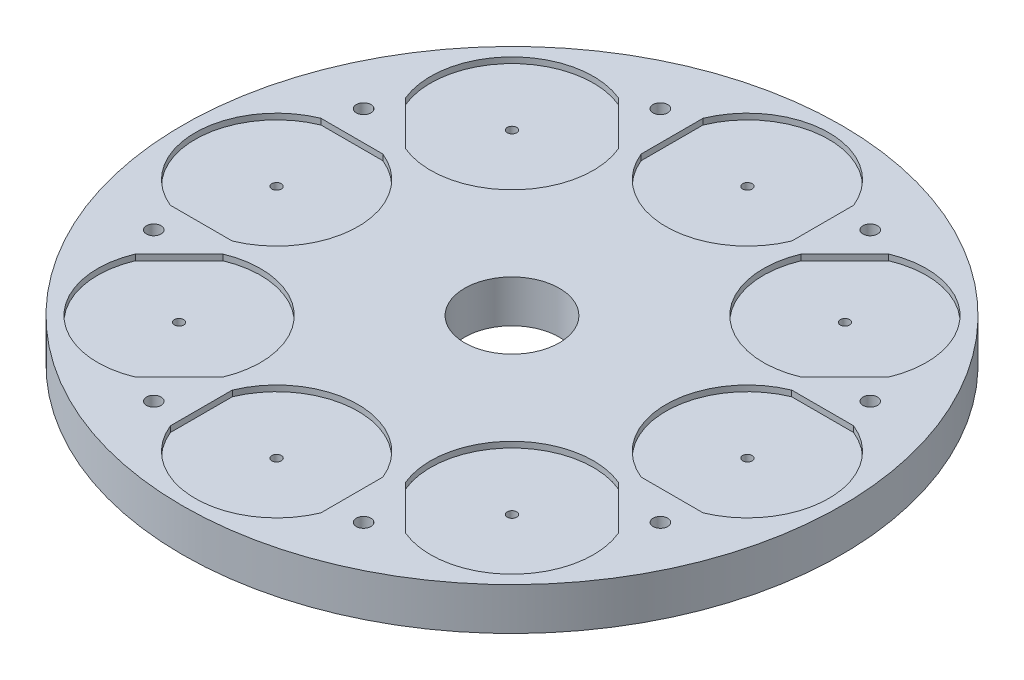
SolidWorks part; units mm, degrees
ref_plane "Front Plane" through (0, 0, 0) normal (0, 0, 1) x (1, 0, 0)
ref_plane "Top Plane" through (0, 0, 0) normal (0, 1, 0) x (1, 0, 0)
ref_plane "Right Plane" through (0, 0, 0) normal (1, 0, 0) x (0, 0, -1)
sketch "Sketch1" plane through (0, 0, 0) normal (0, 1, 0) x (1, 0, 0)
  line L0 (70, 0) -> (50, 0) construction
  circle A0 centre (0, 0) radius 70
  circle A1 centre (50, 0) radius 12
  circle A2 centre (35.3553, -35.3553) radius 12
  circle A3 centre (0, -50) radius 12
  circle A4 centre (-35.3553, -35.3553) radius 12
  circle A5 centre (-50, 0) radius 12
  circle A6 centre (-35.3553, 35.3553) radius 12
  circle A7 centre (0, 50) radius 12
  circle A8 centre (35.3553, 35.3553) radius 12
  point P23 (0, 0)
  dimension "D1" = 140
  dimension "D3" = 24
  dimension "D2" = 20
  dimension "D4" = 8
extrude "Boss-Extrude1" add sketch "Sketch1" along normal blind 25
sketch "Sketch2" plane through (0, 25, 0) normal (0, 1, 0) x (1, 0, 0)
  line L0 (50, 0) -> (50, 16) construction
  line L1 (50, 16) -> (43.4205, 16)
  line L2 (50, 16) -> (56.5795, 16)
  line L3 (32.7, 0) -> (67.3, 0) construction
  line L4 (50, -16) -> (56.5795, -16)
  line L5 (50, -16) -> (43.4205, -16)
  line L6 (46.669, -24.0416) -> (42.0166, -19.3892)
  line L7 (24.0416, -46.669) -> (19.3892, -42.0166)
  line L8 (24.0416, -46.669) -> (28.694, -51.3215)
  line L9 (46.669, -24.0416) -> (51.3215, -28.694)
  line L10 (16, -50) -> (16, -43.4205)
  line L11 (-16, -50) -> (-16, -43.4205)
  line L12 (-16, -50) -> (-16, -56.5795)
  line L13 (16, -50) -> (16, -56.5795)
  line L14 (-24.0416, -46.669) -> (-19.3892, -42.0166)
  line L15 (-46.669, -24.0416) -> (-42.0166, -19.3892)
  line L16 (-46.669, -24.0416) -> (-51.3215, -28.694)
  line L17 (-24.0416, -46.669) -> (-28.694, -51.3215)
  line L18 (-50, -16) -> (-43.4205, -16)
  line L19 (-50, 16) -> (-43.4205, 16)
  line L20 (-50, 16) -> (-56.5795, 16)
  line L21 (-50, -16) -> (-56.5795, -16)
  line L22 (-46.669, 24.0416) -> (-42.0166, 19.3892)
  line L23 (-24.0416, 46.669) -> (-19.3892, 42.0166)
  line L24 (-24.0416, 46.669) -> (-28.694, 51.3215)
  line L25 (-46.669, 24.0416) -> (-51.3215, 28.694)
  line L26 (-16, 50) -> (-16, 43.4205)
  line L27 (16, 50) -> (16, 43.4205)
  line L28 (16, 50) -> (16, 56.5795)
  line L29 (-16, 50) -> (-16, 56.5795)
  line L30 (24.0416, 46.669) -> (19.3892, 42.0166)
  line L31 (46.669, 24.0416) -> (42.0166, 19.3892)
  line L32 (46.669, 24.0416) -> (51.3215, 28.694)
  line L33 (24.0416, 46.669) -> (28.694, 51.3215)
  arc A0 (43.4205, 16) -> (43.4205, -16) centre (50, 0) ccw
  arc A1 (56.5795, -16) -> (56.5795, 16) centre (50, 0) ccw
  arc A2 (42.0166, -19.3892) -> (19.3892, -42.0166) centre (35.3553, -35.3553) ccw
  arc A3 (28.694, -51.3215) -> (51.3215, -28.694) centre (35.3553, -35.3553) ccw
  arc A4 (16, -43.4205) -> (-16, -43.4205) centre (0, -50) ccw
  arc A5 (-16, -56.5795) -> (16, -56.5795) centre (0, -50) ccw
  arc A6 (-19.3892, -42.0166) -> (-42.0166, -19.3892) centre (-35.3553, -35.3553) ccw
  arc A7 (-51.3215, -28.694) -> (-28.694, -51.3215) centre (-35.3553, -35.3553) ccw
  arc A8 (-43.4205, -16) -> (-43.4205, 16) centre (-50, 0) ccw
  arc A9 (-56.5795, 16) -> (-56.5795, -16) centre (-50, 0) ccw
  arc A10 (-42.0166, 19.3892) -> (-19.3892, 42.0166) centre (-35.3553, 35.3553) ccw
  arc A11 (-28.694, 51.3215) -> (-51.3215, 28.694) centre (-35.3553, 35.3553) ccw
  arc A12 (-16, 43.4205) -> (16, 43.4205) centre (0, 50) ccw
  arc A13 (16, 56.5795) -> (-16, 56.5795) centre (0, 50) ccw
  arc A14 (19.3892, 42.0166) -> (42.0166, 19.3892) centre (35.3553, 35.3553) ccw
  arc A15 (51.3215, 28.694) -> (28.694, 51.3215) centre (35.3553, 35.3553) ccw
  point P61 (0, 0)
  dimension "D1" = 34.6
  dimension "D2" = 16
  dimension "D3" = 8
extrude "Cut-Extrude1" cut sketch "Sketch2" against normal blind 10
ref_plane "Plane1" through (0, 10, 0) normal (0, 1, 0) x (1, 0, 0)
split "Split1" trim tools "Plane1" bodies to split 102 resulting bodies 103 104
delete or keep bodies "Body-Delete/Keep 1" type delete bodies bodies 104
sketch "Sketch3" plane through (0, 10, 0) normal (0, -1, 0) x (1, 0, 0)
  circle A0 centre (0, 0) radius 20
  dimension "D1" = 40
extrude "Cut-Extrude2" cut sketch "Sketch3" against normal blind 7.5
sketch "Sketch4" plane through (0, 25, 0) normal (0, 1, 0) x (1, 0, 0)
  circle A0 centre (0, 0) radius 70
extrude "Cut-Extrude3" cut sketch "Sketch4" against normal blind 6
sketch "Sketch5" plane through (0, 19, 0) normal (0, 1, 0) x (1, 0, 0)
  line L0 (-70, 0) -> (70, 0) construction
  line L1 (0, 4) -> (0, -4) construction
  circle A1 centre (0, 0) radius 70 construction
  circle A2 centre (0, -4) radius 1.5
  circle A3 centre (0, 4) radius 1.5
  circle A4 centre (-4, 0) radius 1.5
  circle A5 centre (4, 0) radius 1.5
  point P11 (0, 0)
  dimension "D1" = 3
  dimension "D3" = 4
  dimension "D2" = 8
extrude "Cut-Extrude4" cut sketch "Sketch5" against normal through all
sketch "Sketch6" plane through (0, 19, 0) normal (0, 1, 0) x (1, 0, 0)
  line L0 (-16, 43.4205) -> (-19.3892, 42.0166) construction
  line L1 (-17.6946, 42.7186) -> (-26.7878, 64.6716) construction
  circle A0 centre (0, 0) radius 70 construction
  circle A1 centre (-22.2868, 53.8051) radius 1.55
  circle A2 centre (22.2868, 53.8051) radius 1.55
  circle A3 centre (53.8051, 22.2868) radius 1.55
  circle A4 centre (53.8051, -22.2868) radius 1.55
  circle A5 centre (22.2868, -53.8051) radius 1.55
  circle A6 centre (-22.2868, -53.8051) radius 1.55
  circle A7 centre (-53.8051, -22.2868) radius 1.55
  circle A8 centre (-53.8051, 22.2868) radius 1.55
  point P19 (0, 0)
  dimension "D1" = 12
  dimension "D3" = 3.1
  dimension "D2" = 21.953
  dimension "D4" = 8
sketch "Sketch7" plane through (0, 17.5, 0) normal (0, -1, 0) x (1, 0, 0)
  circle A0 centre (0, 0) radius 20
extrude "Boss-Extrude2" add sketch "Sketch7" along normal up to surface and the other way up to surface up to face at (0, 10, -20) other way up to face at (0, 19, 5.5)
sketch "Sketch9" plane through (0, 10, 0) normal (0, -1, 0) x (1, 0, 0)
  circle A0 centre (0, 50) radius 12
  circle A1 centre (0, 50) radius 2.4904
  circle A2 centre (35.3553, 35.3553) radius 2.4904
  circle A3 centre (35.3553, 35.3553) radius 12
  circle A4 centre (50, 0) radius 2.4904
  circle A5 centre (50, 0) radius 12
  circle A6 centre (35.3553, -35.3553) radius 2.4904
  circle A7 centre (35.3553, -35.3553) radius 12
  circle A8 centre (0, -50) radius 2.4904
  circle A9 centre (0, -50) radius 12
  circle A10 centre (-35.3553, -35.3553) radius 2.4904
  circle A11 centre (-35.3553, -35.3553) radius 12
  circle A12 centre (-50, 0) radius 2.4904
  circle A13 centre (-50, 0) radius 12
  circle A14 centre (-35.3553, 35.3553) radius 2.4904
  circle A15 centre (-35.3553, 35.3553) radius 12
  point P28 (0, 0)
  dimension "D1" = 8
extrude "Boss-Extrude3" add sketch "Sketch9" against normal up to surface (5 mm away) up to face at (50, 15, 12)
extrude "Cut-Extrude5" cut sketch "Sketch6" against normal through all
sketch "Sketch10" plane through (0, 15, 0) normal (0, 1, 0) x (1, 0, 0)
  line L0 (16, -56.5795) -> (16, -43.4205)
  line L1 (-16, -56.5795) -> (-16, -43.4205)
  line L16 (-28.694, -51.3215) -> (-19.3892, -42.0166)
  line L17 (-51.3215, -28.694) -> (-42.0166, -19.3892)
  line L18 (-56.5795, -16) -> (-43.4205, -16)
  line L19 (-56.5795, 16) -> (-43.4205, 16)
  line L20 (-51.3215, 28.694) -> (-42.0166, 19.3892)
  line L21 (-28.694, 51.3215) -> (-19.3892, 42.0166)
  line L22 (-16, 56.5795) -> (-16, 43.4205)
  line L23 (16, 56.5795) -> (16, 43.4205)
  line L24 (28.694, 51.3215) -> (19.3892, 42.0166)
  line L25 (51.3215, 28.694) -> (42.0166, 19.3892)
  line L26 (56.5795, 16) -> (43.4205, 16)
  line L27 (56.5795, -16) -> (43.4205, -16)
  line L28 (51.3215, -28.694) -> (42.0166, -19.3892)
  line L29 (28.694, -51.3215) -> (19.3892, -42.0166)
  arc A0 (16, -43.4205) -> (-16, -43.4205) centre (0, -50) ccw
  arc A1 (-16, -56.5795) -> (16, -56.5795) centre (0, -50) ccw
  circle A16 centre (0, -50) radius 2.4904
  arc A17 (-19.3892, -42.0166) -> (-42.0166, -19.3892) centre (-35.3553, -35.3553) ccw
  arc A18 (-51.3215, -28.694) -> (-28.694, -51.3215) centre (-35.3553, -35.3553) ccw
  circle A19 centre (-35.3553, -35.3553) radius 2.4904
  arc A20 (-43.4205, -16) -> (-43.4205, 16) centre (-50, 0) ccw
  arc A21 (-56.5795, 16) -> (-56.5795, -16) centre (-50, 0) ccw
  circle A22 centre (-50, 0) radius 2.4904
  arc A23 (-42.0166, 19.3892) -> (-19.3892, 42.0166) centre (-35.3553, 35.3553) ccw
  arc A24 (-28.694, 51.3215) -> (-51.3215, 28.694) centre (-35.3553, 35.3553) ccw
  circle A25 centre (-35.3553, 35.3553) radius 2.4904
  arc A26 (-16, 43.4205) -> (16, 43.4205) centre (0, 50) ccw
  arc A27 (16, 56.5795) -> (-16, 56.5795) centre (0, 50) ccw
  circle A28 centre (0, 50) radius 2.4904
  arc A29 (19.3892, 42.0166) -> (42.0166, 19.3892) centre (35.3553, 35.3553) ccw
  arc A30 (51.3215, 28.694) -> (28.694, 51.3215) centre (35.3553, 35.3553) ccw
  circle A31 centre (35.3553, 35.3553) radius 2.4904
  arc A32 (43.4205, 16) -> (43.4205, -16) centre (50, 0) ccw
  arc A33 (56.5795, -16) -> (56.5795, 16) centre (50, 0) ccw
  circle A34 centre (50, 0) radius 2.4904
  arc A35 (42.0166, -19.3892) -> (19.3892, -42.0166) centre (35.3553, -35.3553) ccw
  arc A36 (28.694, -51.3215) -> (51.3215, -28.694) centre (35.3553, -35.3553) ccw
  circle A37 centre (35.3553, -35.3553) radius 2.4904
  point P49 (0, 0)
  point P58 (0, 0)
  dimension "D1" = 8
extrude "Boss-Extrude5" add sketch "Sketch10" along normal blind 2.76
sketch "Sketch11" plane through (0, 19, 0) normal (0, 1, 0) x (1, 0, 0)
  circle A0 centre (0, 0) radius 10.0532
extrude "Cut-Extrude7" cut sketch "Sketch11" against normal through all
sketch "Sketch12" plane through (0, 10, 0) normal (0, -1, 0) x (1, 0, 0)
  circle A1 centre (-35.3553, 35.3553) radius 2.4904
  circle A2 centre (-35.3553, 35.3553) radius 1.75
  circle A3 centre (0, 50) radius 2.4904
  circle A4 centre (0, 50) radius 1.75
  circle A5 centre (35.3553, 35.3553) radius 2.4904
  circle A6 centre (35.3553, 35.3553) radius 1.75
  circle A7 centre (50, 0) radius 2.4904
  circle A8 centre (50, 0) radius 1.75
  circle A9 centre (35.3553, -35.3553) radius 2.4904
  circle A10 centre (35.3553, -35.3553) radius 1.75
  circle A11 centre (0, -50) radius 2.4904
  circle A12 centre (0, -50) radius 1.75
  circle A13 centre (-35.3553, -35.3553) radius 2.4904
  circle A14 centre (-35.3553, -35.3553) radius 1.75
  circle A15 centre (-50, 0) radius 2.4904
  circle A16 centre (-50, 0) radius 1.75
  point P28 (0, 0)
  dimension "D1" = 3.5
  dimension "D2" = 8
extrude "Boss-Extrude6" add sketch "Sketch12" against normal up to surface (7.76 mm away) up to face at (0, 17.76, 50)
sketch "Sketch13" plane through (0, 10, 0) normal (0, -1, 0) x (1, 0, 0)
  circle A0 centre (-35.3553, 35.3553) radius 1.75
  circle A1 centre (-35.3553, 35.3553) radius 1
  circle A2 centre (0, 50) radius 1.75
  circle A3 centre (0, 50) radius 1
  circle A4 centre (35.3553, 35.3553) radius 1.75
  circle A5 centre (35.3553, 35.3553) radius 1
  circle A6 centre (50, 0) radius 1.75
  circle A7 centre (50, 0) radius 1
  circle A8 centre (35.3553, -35.3553) radius 1.75
  circle A9 centre (35.3553, -35.3553) radius 1
  circle A10 centre (0, -50) radius 1.75
  circle A11 centre (0, -50) radius 1
  circle A12 centre (-35.3553, -35.3553) radius 1.75
  circle A13 centre (-35.3553, -35.3553) radius 1
  circle A14 centre (-50, 0) radius 1.75
  circle A15 centre (-50, 0) radius 1
  point P28 (0, 0)
  dimension "D1" = 2
  dimension "D2" = 8
extrude "Boss-Extrude7" add sketch "Sketch13" against normal up to surface (7.76 mm away) and the other way blind 5 up to face at (35.3553, 17.76, 35.3553)
